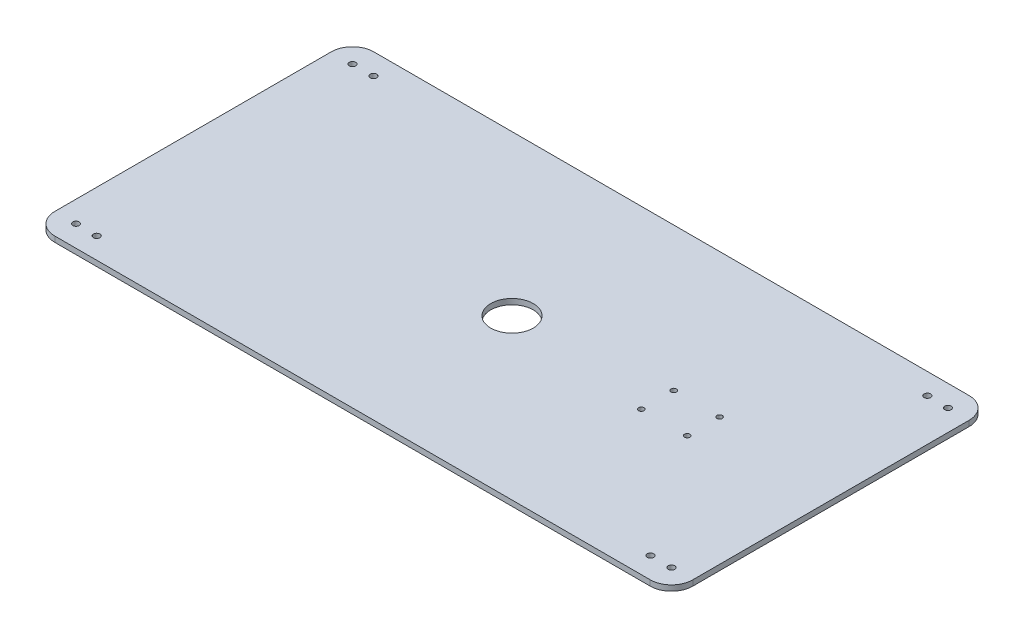
SolidWorks part; units mm, degrees
ref_plane "Front Plane" through (0, 0, 0) normal (0, 0, 1) x (1, 0, 0)
ref_plane "Top Plane" through (0, 0, 0) normal (0, 1, 0) x (1, 0, 0)
ref_plane "Right Plane" through (0, 0, 0) normal (1, 0, 0) x (0, 0, -1)
sketch "Sketch1" plane through (0, 0, 0) normal (0, 1, 0) x (1, 0, 0)
  line L1 (0, 0) -> (300, 0)
  line L2 (0, 0) -> (0, -150)
  line L3 (0, -150) -> (300, -150)
  line L4 (300, 0) -> (300, -150)
  dimension "D1" = 150
  dimension "D2" = 300
extrude "Boss-Extrude1" add sketch "Sketch1" along normal blind 2.6 contours L1 L4 L3 L2
fillet "Fillet1" radius 10 4 edges at (0, 1.3, 0) (0, 1.3, 150) (300, 1.3, 150) (300, 1.3, 0)
sketch "Sketch6" plane through (0, 0, 0) normal (0, -1, 0) x (1, 0, 0)
  line L0 (300, 10) -> (300, 140) construction
  line L1 (10, 0) -> (290, 0) construction
  circle A0 centre (290, 10) radius 1.5
  dimension "D1" = 3
  dimension "D2" = 10
  dimension "D3" = 10
ref_plane "Plane1" through (150, 0, 0) normal (1, 0, 0) x (0, 0, -1)
extrude "Cut-Extrude6" cut sketch "Sketch6" against normal blind 2.6 contours A0
ref_plane "Plane14" through (0, 0, 75) normal (0, 0, 1) x (1, 0, 0)
mirror "Mirror5" about plane through (150, 0, 0) normal (1, 0, 0) of "Cut-Extrude6"
mirror "Mirror6" about plane through (0, 0, 75) normal (0, 0, 1) of "Mirror5"
sketch "Sketch15" plane through (0, 0, 0) normal (0, -1, 0) x (1, 0, 0)
  line L0 (150, 0) -> (150, 150) construction
  line L2 (0, 75) -> (300, 75) construction
  line L4 (0, 10) -> (0, 140) construction
  line L5 (300, 10) -> (300, 140) construction
  line L6 (10, 0) -> (290, 0) construction
  line L7 (10, 150) -> (290, 150) construction
  circle A0 centre (150, 75) radius 10
  dimension "D1" = 20
extrude "Cut-Extrude14" cut sketch "Sketch15" against normal through all contours A0
sketch "Sketch20" plane through (0, 2.6, 0) normal (0, 1, 0) x (1, 0, 0)
  line L0 (-1.43, -75) -> (1.43, -75) construction
  line L1 (218.41, -67.38) -> (218.41, 0) construction
  line L2 (10, 0) -> (290, 0) construction
  line L3 (218.41, 0) -> (218.41, -150) construction
  line L4 (10, -150) -> (290, -150) construction
  line L5 (240, -67.38) -> (240, 0) construction
  line L6 (240, 0) -> (240, -100.7424) construction
  line L7 (300, -10) -> (300, -140) construction
  circle A0 centre (218.41, -67.38) radius 1.27
  circle A1 centre (240, -67.38) radius 1.27
  circle A2 centre (218.41, -82.62) radius 1.27
  circle A3 centre (240, -82.62) radius 1.27
  point P20 (280, -100.7424)
  dimension "D1" = 7.62
  dimension "D2" = 7.62
  dimension "D4" = 7.62
  dimension "D7" = 2.54
  dimension "D8" = 2.54
  dimension "D9" = 2.54
  dimension "D10" = 2.54
  dimension "D3" = 21.59
  dimension "D5" = 7.62
  dimension "D6" = 60
extrude "Cut-Extrude15" cut sketch "Sketch20" against normal through all
sketch "Sketch23" plane through (0, 2.6, 0) normal (0, 1, 0) x (1, 0, 0)
  circle A0 centre (19.812, -9.906) radius 1.524
extrude "Cut-Extrude16" cut sketch "Sketch23" against normal blind 2.6
mirror "Mirror7" about plane through (150, 0, 0) normal (1, 0, 0) of "Cut-Extrude16"
mirror "Mirror8" about plane through (0, 0, 75) normal (0, 0, 1) of "Mirror7"
